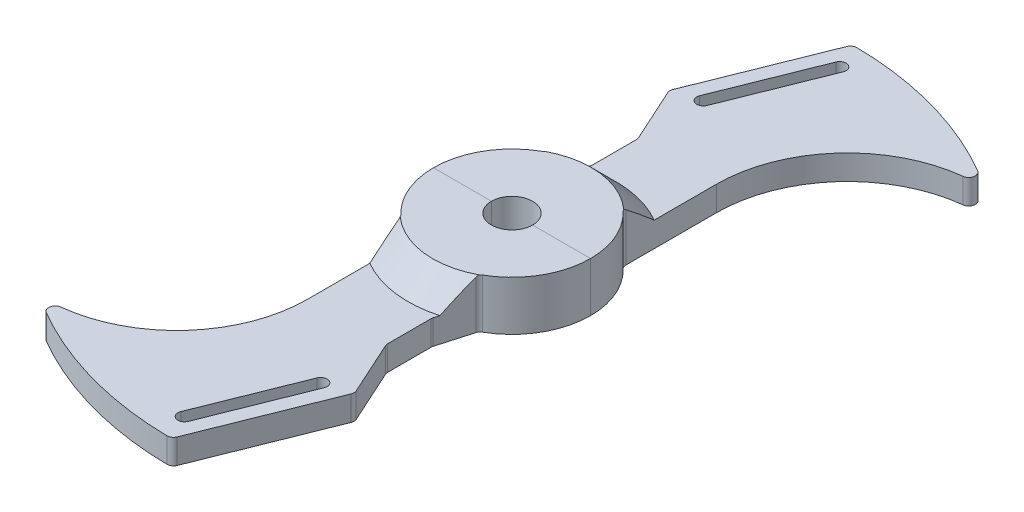
SolidWorks part; units mm, degrees
ref_plane "Front" through (0, 0, 0) normal (0, 0, 1) x (1, 0, 0)
ref_plane "Top" through (0, 0, 0) normal (0, 1, 0) x (1, 0, 0)
ref_plane "Right" through (0, 0, 0) normal (1, 0, 0) x (0, 0, -1)
ref_axis "Axis1" through (0, 50, 0) along (0, -1, 0)
sketch "Sketch1" plane through (0, 0, 0) normal (0, 1, 0) x (1, 0, 0)
  line L0 (0, 41.275) -> (0, -41.275) construction
  line L1 (2.5, 0) -> (6.35, 0) construction
  line L4 (21.1797, 35.4946) -> (24.8259, 33.0473) construction
  line L6 (6.35, 7.0995) -> (6.35, 18.415)
  line L7 (0, 41.275) -> (-6.35, 25.4)
  line L8 (-3.175, 18.415) -> (6.35, 18.415) construction
  line L9 (-3.175, 12.8692) -> (-4.445, 8.4242)
  line L10 (-6.35, 0) -> (-2.5, 0)
  line L11 (-4.445, 8.4242) -> (-4.445, 0) construction
  line L12 (6.35, 7.0995) -> (6.35, 0) construction
  line L13 (-6.35, 25.4) -> (-6.35, 0) construction
  line L14 (-3.175, 12.8692) -> (-3.175, 18.415)
  line L15 (-3.175, 18.415) -> (-6.35, 25.4)
  line L16 (-9.525, 0) -> (-2.5, 0)
  line L17 (2.5, 0) -> (9.525, 0)
  circle A0 centre (0, 0) radius 41.275 construction
  arc A4 (0, 41.275) -> (23.0028, 34.2709) centre (0, 0) cw
  arc A5 (6.35, 18.415) -> (23.0028, 34.2709) centre (22.225, 18.415) cw
  arc A6 (-4.445, 8.4242) -> (-9.525, 0) centre (0, 0) ccw
  arc A7 (2.5, 0) -> (-2.5, 0) centre (0, 0) ccw
  arc A8 (9.525, 0) -> (6.35, 7.0995) centre (0, 0) ccw
  point P8 (0, 0)
  point P22 (23.0028, 34.2709)
  dimension "D1" = 82.55
  dimension "D3" = 4.445
  dimension "D5" = 3.175
  dimension "D6" = 6.985
  dimension "D7" = 15.875
  dimension "D9" = 19.05
  dimension "D10" = 5
  dimension "D2" = 6.35
  dimension "D4" = 15.875
  dimension "D8" = 4.445
  dimension "D11" = 6.35
extrude "Boss-Extrude1" add sketch "Sketch1" along normal blind 6 contours L17 A8 L6 A5 A4 L7 L15 L14 L9 A6 L16 L10 A7 region at (3.0803, 0, -21.7757)
fillet "Fillet1" radius 0.7937 7 edges at (-4.445, 3, -8.4242) (-3.175, 3, -12.8692) (-3.175, 3, -18.415) (6.35, 3, -7.0995) (-6.35, 3, -25.4) (0, 3, -41.275) (23.0028, 3, -34.2709)
sketch "Sketch3" plane through (0, 6, 0) normal (0, 1, 0) x (1, 0, 0)
  line L0 (-3.2126, 33.2436) -> (9.6465, 28.0999) construction
  line L1 (-0.201, 40.7725) -> (-6.2241, 25.7147) construction
  line L2 (-3.2126, 26.4044) -> (1.5041, 38.1961) construction
  line L3 (-3.9495, 26.6992) -> (0.7671, 38.4909)
  line L4 (-2.4756, 26.1096) -> (2.2411, 37.9013)
  arc A0 (20.4619, 34.1918) -> (6.35, 18.415) centre (22.225, 18.415) ccw construction
  arc A1 (-3.9495, 26.6992) -> (-2.4756, 26.1096) centre (-3.2126, 26.4044) ccw
  arc A2 (2.2411, 37.9013) -> (0.7671, 38.4909) centre (1.5041, 38.1961) ccw
  point P9 (-0.8542, 32.3003)
  dimension "D1" = 2.54
  dimension "D2" = 12.7
  dimension "D3" = 1.5875
extrude "Cut-Extrude2" cut sketch "Sketch3" against normal through all
sketch "Sketch5" plane through (0, 6, 0) normal (0, 1, 0) x (1, 0, 0)
  line L7 (-0.201, 40.7725) -> (-6.2241, 25.7147)
  line L8 (-6.2097, 25.0914) -> (-3.2461, 18.5715)
  line L9 (-3.175, 18.2431) -> (-3.175, 12.9804)
  line L10 (-3.2055, 12.7623) -> (-4.3541, 8.7424)
  line L11 (-9.525, 0) -> (-2.5, 0)
  line L12 (2.5, 0) -> (9.525, 0)
  line L13 (6.35, 7.446) -> (6.35, 18.415)
  line L14 (-0.201, 40.7725) -> (-6.2241, 25.7147)
  line L15 (-6.2097, 25.0914) -> (-3.2461, 18.5715)
  line L16 (-3.175, 18.2431) -> (-3.175, 12.9804)
  line L17 (-3.2055, 12.7623) -> (-4.3541, 8.7424)
  line L20 (6.35, 7.446) -> (6.35, 18.415)
  arc A0 (-4.4927, 8.4706) -> (6.4136, 7.1347) centre (0.009, 0.0353) cw
  arc A1 (-4.7237, 8.2712) -> (-4.3541, 8.7424) centre (-5.1173, 8.9605) ccw construction
  arc A2 (6.35, 7.446) -> (6.5942, 6.8733) centre (7.1437, 7.446) ccw construction
  arc A3 (-4.7237, 8.2712) -> (-9.525, 0) centre (0, 0) ccw construction
  arc A16 (-6.2241, 25.7147) -> (-6.2097, 25.0914) centre (-5.4871, 25.4199) ccw
  arc A17 (-3.175, 18.2431) -> (-3.2461, 18.5715) centre (-3.9687, 18.2431) ccw
  arc A18 (-3.2055, 12.7623) -> (-3.175, 12.9804) centre (-3.9687, 12.9804) ccw
  arc A19 (-4.7237, 8.2712) -> (-4.3541, 8.7424) centre (-5.1173, 8.9605) ccw
  arc A20 (-4.7237, 8.2712) -> (-9.525, 0) centre (0, 0) ccw
  arc A21 (2.5, 0) -> (-2.5, 0) centre (0, 0) ccw
  arc A22 (9.525, 0) -> (6.5942, 6.8733) centre (0, 0) ccw
  arc A23 (6.35, 7.446) -> (6.5942, 6.8733) centre (7.1437, 7.446) ccw
  arc A24 (20.4619, 34.1918) -> (6.35, 18.415) centre (22.225, 18.415) ccw
  arc A25 (20.4619, 34.1918) -> (20.7732, 35.6665) centre (20.3737, 34.9806) ccw
  arc A26 (20.7732, 35.6665) -> (0.5465, 41.2714) centre (0, 0) ccw
  arc A27 (0.5465, 41.2714) -> (-0.201, 40.7725) centre (0.536, 40.4777) ccw
  arc A28 (-6.2241, 25.7147) -> (-6.2097, 25.0914) centre (-5.4871, 25.4199) ccw
  arc A29 (-3.175, 18.2431) -> (-3.2461, 18.5715) centre (-3.9687, 18.2431) ccw
  arc A30 (-3.2055, 12.7623) -> (-3.175, 12.9804) centre (-3.9687, 12.9804) ccw
  arc A31 (-4.7237, 8.2712) -> (-4.3541, 8.7424) centre (-5.1173, 8.9605) ccw
  arc A35 (6.35, 7.446) -> (6.5942, 6.8733) centre (7.1437, 7.446) ccw
  arc A36 (20.4619, 34.1918) -> (6.35, 18.415) centre (22.225, 18.415) ccw
  arc A37 (20.4619, 34.1918) -> (20.7732, 35.6665) centre (20.3737, 34.9806) ccw
  arc A38 (20.7732, 35.6665) -> (0.5465, 41.2714) centre (0, 0) ccw
  arc A39 (0.5465, 41.2714) -> (-0.201, 40.7725) centre (0.536, 40.4777) ccw
  arc M20 (-2.4756, 26.1096) -> (-3.9495, 26.6992) centre (-3.2126, 26.4044) cw
  line M21 (-3.9495, 26.6992) -> (0.7671, 38.4909)
  arc M22 (0.7671, 38.4909) -> (2.2411, 37.9013) centre (1.5041, 38.1961) cw
  line M23 (2.2411, 37.9013) -> (-2.4756, 26.1096)
  line M24 (-0.201, 40.7725) -> (-6.2241, 25.7147)
  arc M25 (-6.2241, 25.7147) -> (-6.2097, 25.0914) centre (-5.4871, 25.4199) ccw
  line M26 (-6.2097, 25.0914) -> (-3.2461, 18.5715)
  arc M27 (-3.2461, 18.5715) -> (-3.175, 18.2431) centre (-3.9687, 18.2431) cw
  line M28 (-3.175, 18.2431) -> (-3.175, 12.9804)
  arc M29 (-3.175, 12.9804) -> (-3.2055, 12.7623) centre (-3.9687, 12.9804) cw
  line M30 (-3.2055, 12.7623) -> (-4.3541, 8.7424)
  arc M31 (-4.3541, 8.7424) -> (-4.7237, 8.2712) centre (-5.1173, 8.9605) cw
  arc M37 (6.5942, 6.8733) -> (6.35, 7.446) centre (7.1437, 7.446) cw
  line M38 (6.35, 7.446) -> (6.35, 18.415)
  arc M39 (6.35, 18.415) -> (20.4619, 34.1918) centre (22.225, 18.415) cw
  arc M40 (20.4619, 34.1918) -> (20.7732, 35.6665) centre (20.3737, 34.9806) ccw
  arc M41 (20.7732, 35.6665) -> (0.5465, 41.2714) centre (0, 0) ccw
  arc M42 (0.5465, 41.2714) -> (-0.201, 40.7725) centre (0.536, 40.4777) ccw
  dimension "D1" = 0
extrude "Cut-Extrude3" cut sketch "Sketch5" against normal blind 3 contours A0 M31 M37 M38 M39 M40 M41 M42 M24 M25 M26 M27 M28 M29 M30 M23 M20 M21 M22 region at (4.223, 6, -26.7885)
chamfer "Chamfer1" distance 3 angle 45 1 edges at (1.1715, 3, -9.5258)
pattern_circular "CirPattern1" count 2 over 360 about axis through (0, 50, 0) along (0, -1, 0) of "Boss-Extrude1"
